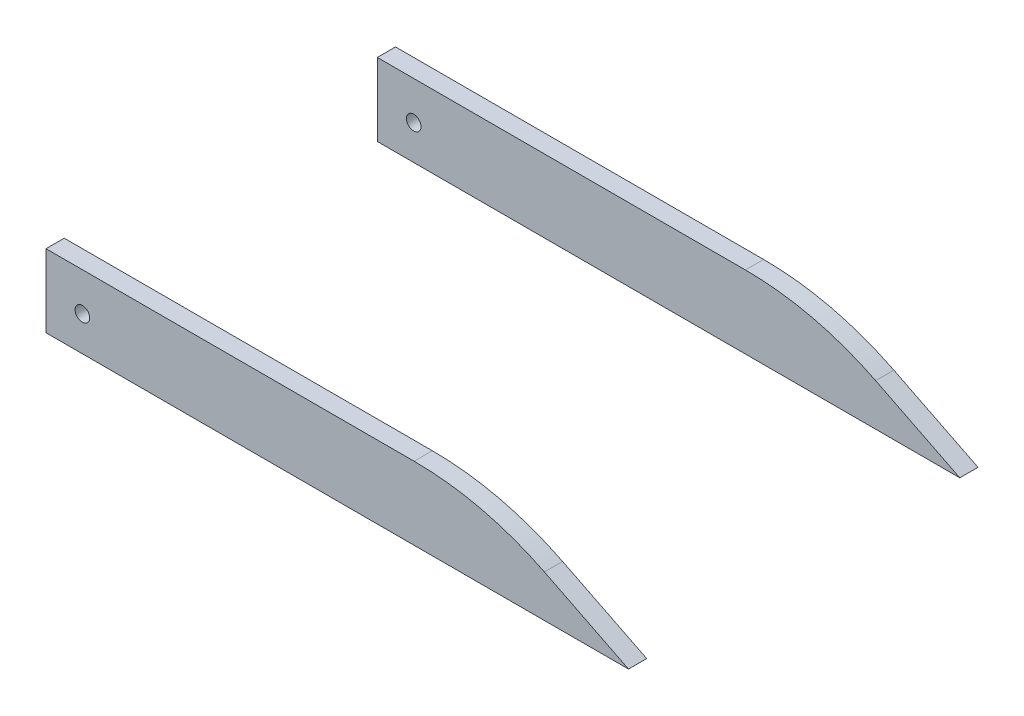
SolidWorks part; units mm, degrees
ref_plane "Front Plane" through (0, 0, 0) normal (0, 0, 1) x (1, 0, 0)
ref_plane "Top Plane" through (0, 0, 0) normal (0, 1, 0) x (1, 0, 0)
ref_plane "Right Plane" through (0, 0, 0) normal (1, 0, 0) x (0, 0, -1)
sketch "Sketch2" plane through (0, 0, 0) normal (0, 0, 1) x (1, 0, 0)
  line L0 (0, 0) -> (0, -20)
  line L1 (0, -20) -> (160, -20)
  line L2 (0, 0) -> (101.1146, 0)
  line L3 (136.8916, -8.4458) -> (160, -20)
  arc A1 (101.1146, 0) -> (136.8916, -8.4458) centre (101.1146, -80) cw
  point P12 (120, 0)
  dimension "D1" = 80
  dimension "D2" = 20
  dimension "D3" = 160
  dimension "D4" = 120
extrude "Boss-Extrude1" add sketch "Sketch2" along normal blind 5 from offset 91
extrude "Boss-Extrude2" add sketch "Sketch2<2>" along normal blind 5 separate body
sketch "Sketch2<2>" plane through (0, 0, 0) normal (0, 0, 1) x (1, 0, 0) same geometry as "Sketch2"
sketch "Sketch3" plane through (0, 0, 5) normal (0, 0, 1) x (1, 0, 0)
  line L0 (101.1146, 0) -> (0, 0) construction
  line L1 (0, 0) -> (0, -20) construction
  circle A0 centre (10, -10.5) radius 2
  dimension "D1" = 4
  dimension "D2" = 10.5
  dimension "D3" = 10
extrude "Cut-Extrude1" cut sketch "Sketch3" against normal through all both and the other way through all
